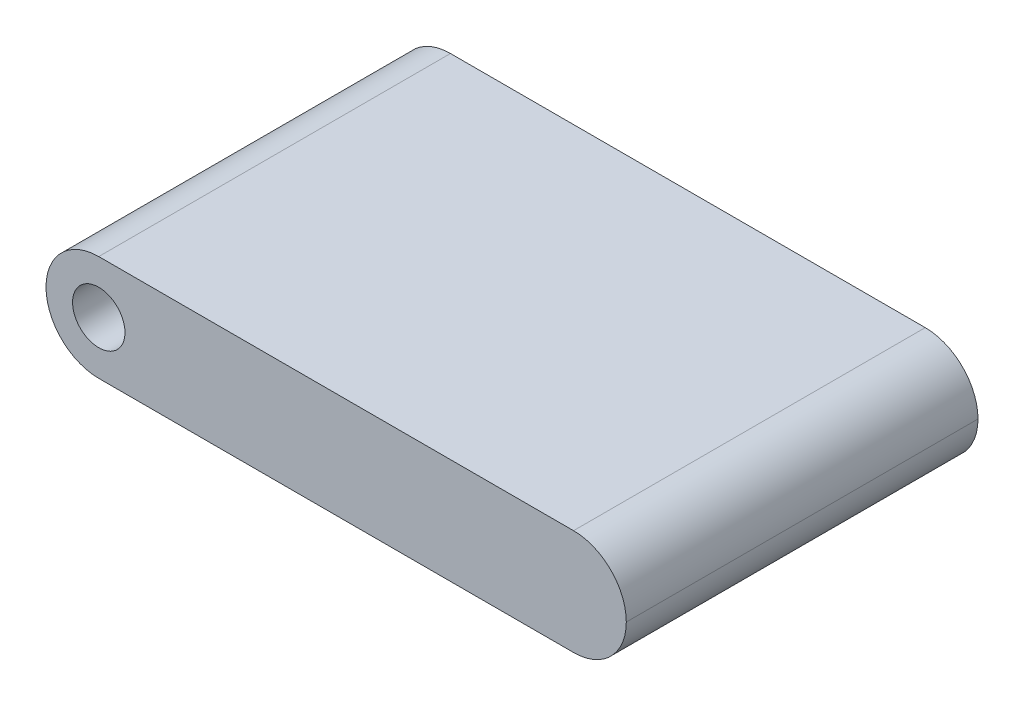
SolidWorks part; units mm, degrees
ref_plane "Front Plane" through (0, 0, 0) normal (0, 0, 1) x (1, 0, 0)
ref_plane "Top Plane" through (0, 0, 0) normal (0, 1, 0) x (1, 0, 0)
ref_plane "Right Plane" through (0, 0, 0) normal (1, 0, 0) x (0, 0, -1)
sketch "Sketch1" plane through (0, 0, 0) normal (0, 0, 1) x (1, 0, 0)
  line L4 (60, 6) -> (-6, 6)
  line L5 (-6, 6) -> (-6, -6)
  line L6 (0, 0) -> (-6, 0) construction
  line L7 (-6, -6) -> (60, -6)
  line L8 (60, -6) -> (60, 6)
  circle A0 centre (0, 0) radius 2.98
  dimension "D1" = 5.96
  dimension "D2" = 12
  dimension "D3" = 60
  dimension "D6" = 6
extrude "Boss-Extrude1" add sketch "Sketch1" along normal mid plane 40
fillet "Fillet2" radius 6 4 edges at (60, -6, 0) (60, 6, 0) (-6, -6, 0) (-6, 6, 0)
